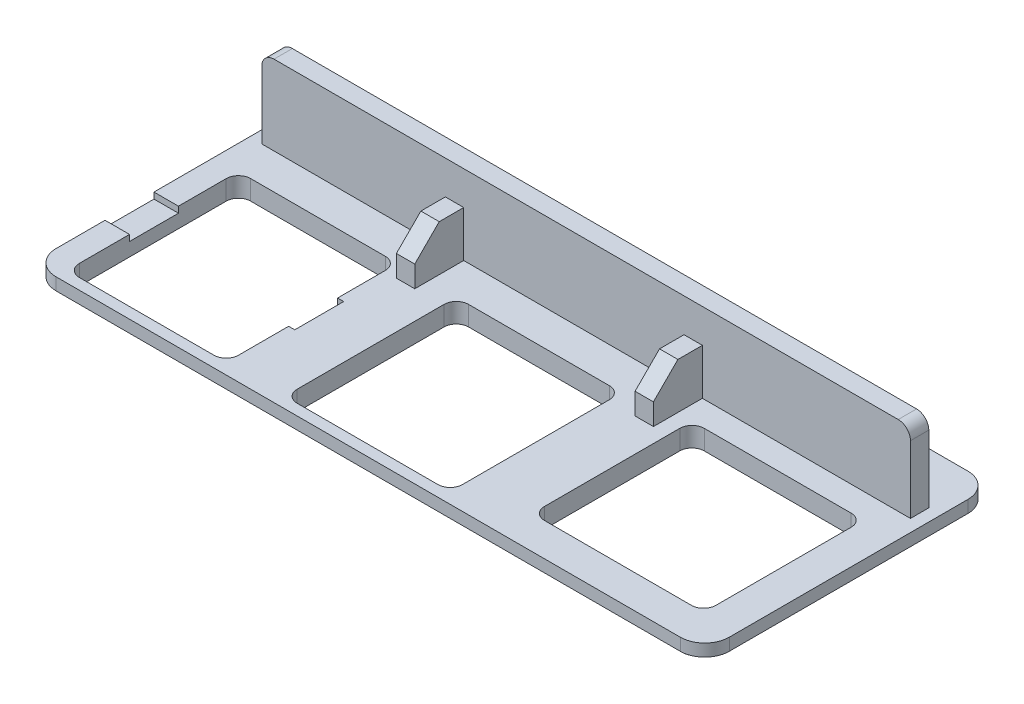
SolidWorks part; units mm, degrees
ref_plane "前视基准面" through (0, 0, 0) normal (0, 0, 1) x (1, 0, 0)
ref_plane "上视基准面" through (0, 0, 0) normal (0, 1, 0) x (1, 0, 0)
ref_plane "右视基准面" through (0, 0, 0) normal (1, 0, 0) x (0, 0, -1)
sketch "草图1" plane through (0, 0, 0) normal (0, 1, 0) x (1, 0, 0)
  line L1 (-27.5, 11.75) -> (27.5, 11.75)
  line L2 (-27.5, 11.75) -> (-27.5, -11.75)
  line L3 (-27.5, -11.75) -> (27.5, -11.75)
  line L4 (27.5, 11.75) -> (27.5, -11.75)
  line L5 (-27.5, 11.75) -> (27.5, -11.75) construction
  line L6 (-27.5, -11.75) -> (27.5, 11.75) construction
  point P0 (0, 0)
  dimension "D1" = 23.5
  dimension "D2" = 55
extrude "凸台-拉伸1" add sketch "草图1" along normal blind 1
fillet "圆角1" radius 2 4 edges at (-27.5, 0.5, 11.75) (27.5, 0.5, 11.75) (-27.5, 0.5, -11.75) (27.5, 0.5, -11.75)
sketch "草图2" plane through (0, 0, 0) normal (0, -1, 0) x (1, 0, 0)
  line L0 (-27.5, -9.75) -> (-27.5, 9.75) construction
  line L1 (-26.5, 11.15) -> (26.5, 11.15)
  line L2 (-26.5, 11.15) -> (-26.5, -11.15)
  line L3 (-26.5, -11.15) -> (26.5, -11.15)
  line L4 (26.5, 11.15) -> (26.5, -11.15)
  line L5 (27.5, 9.75) -> (27.5, -9.75) construction
  line L6 (-25.5, 11.75) -> (25.5, 11.75) construction
  line L7 (25.5, -11.75) -> (-25.5, -11.75) construction
  point P4 (-13.6287, 2.2469)
  point P5 (0, 0)
  point P6 (27.4142, -11.4142)
  point P7 (26.2742, -11.1642)
  point P8 (25.7973, -11.0618)
  point P9 (26.2027, -11.2288)
  point P10 (-26.2374, 11.2578)
  dimension "D1" = 1
  dimension "D2" = 1
  dimension "D3" = 0.6
  dimension "D4" = 0.6
extrude "凸台-拉伸2" add sketch "草图2" along normal blind 0.6
sketch "草图3" plane through (0, -0.6, 0) normal (0, -1, 0) x (1, 0, 0)
  line L1 (-25.5, 10.85) -> (-12.5, 10.85)
  line L2 (-25.5, 10.85) -> (-25.5, -3.15)
  line L3 (-25.5, -3.15) -> (-12.5, -3.15)
  line L4 (-12.5, 10.85) -> (-12.5, -3.15)
  line L5 (-7.7, 10.85) -> (5.8, 10.85)
  line L6 (-7.7, 10.85) -> (-7.7, -3.15)
  line L7 (-7.7, -3.15) -> (5.8, -3.15)
  line L8 (5.8, 10.85) -> (5.8, -3.15)
  line L9 (10.7, 9.0414) -> (24.7, 9.0414)
  line L10 (10.7, 9.0414) -> (10.7, -4.0086)
  line L11 (10.7, -4.0086) -> (24.7, -4.0086)
  line L12 (24.7, 9.0414) -> (24.7, -4.0086)
  line L15 (-27.5, -9.75) -> (-27.5, 9.75) construction
  line L16 (-25.5, 11.75) -> (25.5, 11.75) construction
  line L17 (27.5, 9.75) -> (27.5, -9.75) construction
  dimension "D1" = 13
  dimension "D2" = 13.5
  dimension "D3" = 14
  dimension "D4" = 2
  dimension "D5" = 0.9
  dimension "D6" = 19.8
  dimension "D7" = 13.05
  dimension "D8" = 2.8
  dimension "D10" = 14
extrude "切除-拉伸1" cut sketch "草图3" against normal blind 3
fillet "圆角2" radius 1 12 edges at (-25.5, 0.2, 10.85) (-12.5, 0.2, 10.85) (-7.7, 0.2, 10.85) (5.8, 0.2, 10.85) (24.7, 0.2, 9.0414) (10.7, 0.2, 9.0414) (24.7, 0.2, -4.0086) (10.7, 0.2, -4.0086) (5.8, 0.2, -3.15) (-7.7, 0.2, -3.15) (-12.5, 0.2, -3.15) (-25.5, 0.2, -3.15)
sketch "草图4" plane through (0, 1, 0) normal (0, 1, 0) x (1, 0, 0)
  line L0 (-27.5, 9.75) -> (-27.5, -9.75) construction
  line L1 (-12, -5.75) -> (-27.5, -5.75)
  line L2 (-12, -5.75) -> (-12, -1.7526)
  line L3 (-12, -1.7526) -> (-27.5, -1.7526)
  line L4 (-27.5, -5.75) -> (-27.5, -1.7526)
  line L5 (-25.5, -11.75) -> (25.5, -11.75) construction
  dimension "D1" = 6
  dimension "D2" = 3.9974
  dimension "D3" = 15.5
extrude "切除-拉伸2" cut sketch "草图4" against normal blind 0.5
sketch "草图5" plane through (0, 1, 0) normal (0, 1, 0) x (1, 0, 0)
  line L1 (26.5, 6.0546) -> (-26.5, 6.0546)
  line L2 (26.5, 6.0546) -> (26.5, 7.5546)
  line L3 (26.5, 7.5546) -> (-26.5, 7.5546)
  line L4 (-26.5, 6.0546) -> (-26.5, 7.5546)
  line L6 (-27.5, 9.75) -> (-27.5, -1.7526) construction
  line L7 (27.5, -9.75) -> (27.5, 9.75) construction
  line L8 (25.5, 11.75) -> (-25.5, 11.75) construction
  dimension "D1" = 1.5
  dimension "D2" = 1
  dimension "D3" = 1
  dimension "D4" = 4.1954
extrude "凸台-拉伸3" add sketch "草图5" along normal blind 6.5
fillet "圆角3" radius 1 2 edges at (-26.5, 7.5, -6.8046) (26.5, 7.5, -6.8046)
sketch "草图6" plane through (0, 1, 0) normal (0, 1, 0) x (1, 0, 0)
  line L0 (-26.5, 6.0546) -> (26.5, 6.0546) construction
  line L1 (9.5, 6.0546) -> (8, 6.0546)
  line L2 (9.5, 6.0546) -> (9.5, 2.0546)
  line L3 (9.5, 2.0546) -> (8, 2.0546)
  line L4 (8, 6.0546) -> (8, 2.0546)
  line L5 (27.5, -9.75) -> (27.5, 9.75) construction
  line L6 (-10, 6.0546) -> (-11.5, 6.0546)
  line L7 (-10, 6.0546) -> (-10, 2.0546)
  line L8 (-10, 2.0546) -> (-11.5, 2.0546)
  line L9 (-11.5, 6.0546) -> (-11.5, 2.0546)
  line L10 (-27.5, -5.75) -> (-27.5, -9.75) construction
  dimension "D1" = 4
  dimension "D2" = 1.5
  dimension "D3" = 18
  dimension "D4" = 16
extrude "凸台-拉伸4" add sketch "草图6" along normal blind 3.75
chamfer "倒角1" distance 2 angle 45 2 edges at (-10.75, 4.75, -2.0546) (8.75, 4.75, -2.0546)
fillet "圆角4" radius 1.5 4 edges at (-26.5, -0.3, -11.15) (26.5, -0.3, -11.15) (26.5, -0.3, 11.15) (-26.5, -0.3, 11.15)
